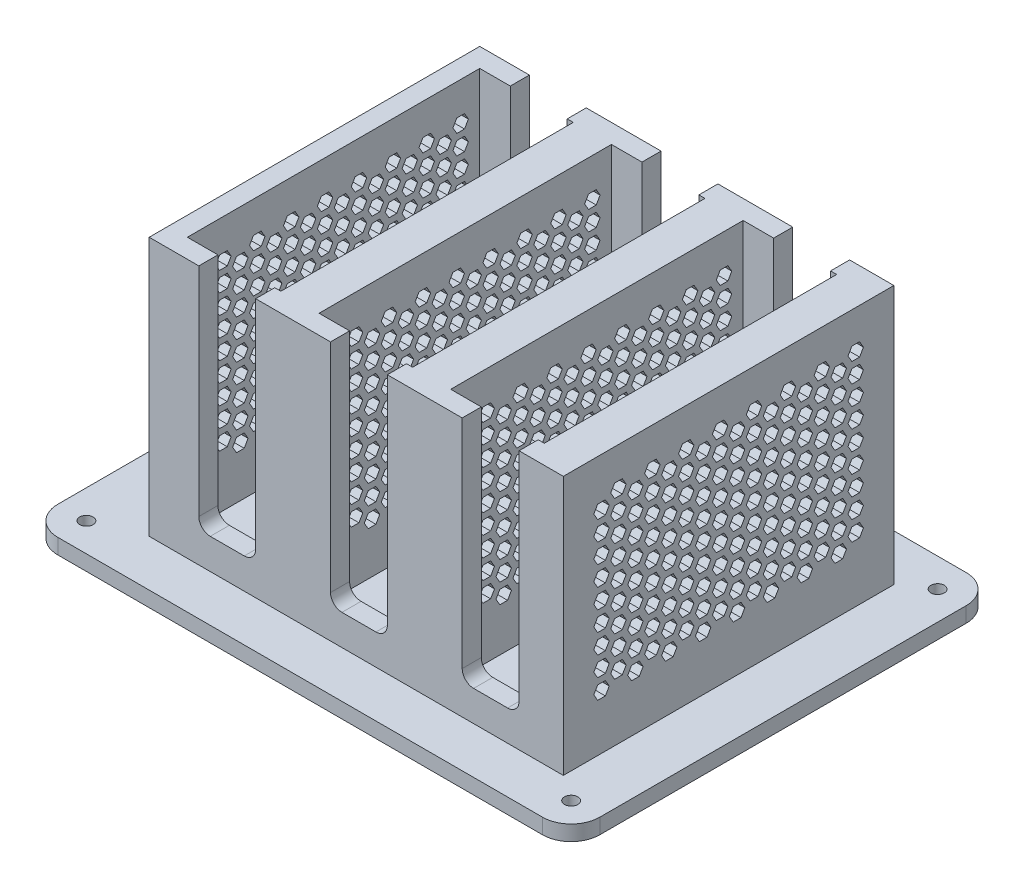
SolidWorks part; units mm, degrees
ref_plane "Front Plane" through (0, 0, 0) normal (0, 0, 1) x (1, 0, 0)
ref_plane "Top Plane" through (0, 0, 0) normal (0, 1, 0) x (1, 0, 0)
ref_plane "Right Plane" through (0, 0, 0) normal (1, 0, 0) x (0, 0, -1)
sketch "Sketch1" plane through (0, 0, 0) normal (0, 1, 0) x (1, 0, 0)
  line L1 (22.25, -38.3) -> (46.75, -38.3) construction
  line L2 (22.25, -38.3) -> (22.25, 38.3) construction
  line L3 (22.25, 38.3) -> (46.75, 38.3) construction
  line L4 (46.75, -38.3) -> (46.75, 38.3) construction
  line L5 (22.25, -38.3) -> (46.75, 38.3) construction
  line L6 (22.25, 38.3) -> (46.75, -38.3) construction
  line L10 (-12.25, 38.3) -> (12.25, 38.3) construction
  line L11 (-55, 0) -> (55, 0) construction
  line L12 (0, -55) -> (0, 55) construction
  line L13 (-71, 55.5) -> (71, -55.5) construction
  line L14 (-12.25, -38.3) -> (-12.25, 38.3) construction
  line L15 (12.25, -38.3) -> (12.25, 38.3) construction
  line L16 (-12.25, -38.3) -> (12.25, -38.3) construction
  line L17 (-46.75, 38.3) -> (-22.25, 38.3) construction
  line L18 (-46.75, -38.3) -> (-46.75, 38.3) construction
  line L19 (-22.25, -38.3) -> (-22.25, 38.3) construction
  line L20 (-46.75, -38.3) -> (-22.25, -38.3) construction
  line L21 (-12.25, 38.3) -> (12.25, -38.3) construction
  line L23 (-63.5, -55.5) -> (63.5, -55.5)
  line L24 (-71, -48) -> (-71, 48)
  line L25 (-63.5, 55.5) -> (63.5, 55.5)
  line L26 (71, -48) -> (71, 48)
  circle A0 centre (-63.5, 48) radius 1.75
  circle A1 centre (-63.5, -48) radius 1.75
  circle A2 centre (63.5, 48) radius 1.75
  circle A3 centre (63.5, -48) radius 1.75
  arc A4 (-63.5, -55.5) -> (-71, -48) centre (-63.5, -48) cw
  arc A5 (63.5, -55.5) -> (71, -48) centre (63.5, -48) ccw
  arc A6 (63.5, 55.5) -> (71, 48) centre (63.5, 48) cw
  arc A7 (-71, 48) -> (-63.5, 55.5) centre (-63.5, 48) cw
  point P0 (34.5, 0)
  point P40 (68, -48)
  point P41 (0, 0)
  point P42 (-63.6306, 48)
  dimension "D4" = 3.5
  dimension "D5" = 3
  dimension "D8" = 7.5
  dimension "D1" = 24.5
  dimension "D2" = 76.6
  dimension "D6" = 10
  dimension "D7" = 127
  dimension "D9" = 96
extrude "Boss-Extrude1" add sketch "Sketch1" along normal blind 4
sketch "Sketch5" plane through (0, 4, 0) normal (0, 1, 0) x (1, 0, 0)
  line L0 (-46.75, -38.3) -> (-46.75, 38.3)
  line L1 (-4.25, 43.3) -> (-4.25, 38.3)
  line L2 (-46.75, -38.3) -> (-38.75, -38.3)
  line L3 (-46.75, -38.3) -> (-22.25, -38.3) construction
  line L4 (-38.75, -38.3) -> (-38.75, -43.3)
  line L5 (-38.75, -43.3) -> (-51.75, -43.3)
  line L6 (-51.75, -43.3) -> (-51.75, 43.3)
  line L7 (-51.75, 43.3) -> (-38.75, 43.3)
  line L8 (-38.75, 43.3) -> (-38.75, 38.3)
  line L9 (-46.75, 38.3) -> (-22.25, 38.3) construction
  line L10 (-38.75, 38.3) -> (-46.75, 38.3)
  line L11 (-46.75, -38.3) -> (-51.75, -38.3) construction
  line L28 (-22.25, 38.3) -> (-23.85, 38.3)
  line L29 (-23.85, 38.3) -> (-23.85, 43.3)
  line L30 (-23.85, 43.3) -> (-4.25, 43.3)
  line L31 (-55, 0) -> (55, 0) construction
  line L32 (-22.25, -38.3) -> (-23.85, -38.3)
  line L33 (-23.85, -38.3) -> (-23.85, -43.3)
  line L34 (-23.85, -43.3) -> (-4.25, -43.3)
  line L35 (-12.25, 38.3) -> (12.25, 38.3) construction
  line L36 (-4.25, 38.3) -> (-12.25, 38.3)
  line L37 (-12.25, 38.3) -> (-12.25, -38.3)
  line L39 (-12.25, -38.3) -> (12.25, -38.3) construction
  line L40 (-4.25, -38.3) -> (-4.25, -43.3)
  line L41 (-22.25, -38.3) -> (-22.25, 38.3)
  line L42 (12.25, -38.3) -> (12.25, 38.3)
  line L43 (12.25, 38.3) -> (10.65, 38.3)
  line L44 (10.65, 38.3) -> (10.65, 43.3)
  line L45 (10.65, 43.3) -> (30.25, 43.3)
  line L46 (30.25, 43.3) -> (30.25, 38.3)
  line L47 (30.25, 38.3) -> (22.25, 38.3)
  line L48 (22.25, 38.3) -> (22.25, -38.3)
  line L49 (22.25, -38.3) -> (30.25, -38.3)
  line L50 (30.25, -38.3) -> (30.25, -43.3)
  line L51 (10.65, -43.3) -> (30.25, -43.3)
  line L52 (10.65, -38.3) -> (10.65, -43.3)
  line L53 (12.25, -38.3) -> (10.65, -38.3)
  line L54 (46.75, -38.3) -> (46.75, 38.3)
  line L55 (46.75, 38.3) -> (45.15, 38.3)
  line L56 (45.15, 38.3) -> (45.15, 43.3)
  line L57 (45.15, 43.3) -> (56.75, 43.3)
  line L60 (56.75, 38.3) -> (56.75, -38.3)
  line L63 (45.15, -43.3) -> (56.75, -43.3)
  line L64 (45.15, -38.3) -> (45.15, -43.3)
  line L65 (46.75, -38.3) -> (45.15, -38.3)
  line L66 (64.75, 43.3) -> (64.75, 38.3) [skipped]
  line L67 (64.75, 38.3) -> (56.75, 38.3) [skipped]
  line L68 (56.75, 38.3) -> (56.75, 43.3)
  line L69 (56.75, -38.3) -> (56.75, -43.3)
  line L70 (-12.25, -38.3) -> (-4.25, -38.3)
  line L72 (64.75, -38.3) -> (64.75, -43.3) [skipped]
  point P26 (-4.5, -46.4399)
  point P34 (-6.2339, 40.5)
  dimension "D1" = 5
  dimension "D2" = 8
  dimension "D3" = 1.6
  dimension "D4" = 3
extrude "Boss-Extrude3" add sketch "Sketch5" along normal blind 67.862
sketch "Sketch6" plane through (0, 4, 0) normal (0, 1, 0) x (1, 0, 0)
  line L1 (-51.75, -43.3) -> (56.75, -43.3)
  line L2 (-51.75, -43.3) -> (-51.75, 43.3)
  line L3 (-51.75, 43.3) -> (56.75, 43.3)
  line L4 (56.75, -43.3) -> (56.75, 43.3)
  line L5 (-46.75, -38.3) -> (46.75, -38.3)
  line L6 (-46.75, -38.3) -> (-46.75, 38.3)
  line L7 (-46.75, 38.3) -> (46.75, 38.3)
  line L8 (46.75, -38.3) -> (46.75, 38.3)
extrude "Boss-Extrude4" add sketch "Sketch6" along normal blind 8
fillet "Fillet1" radius 3 12 edges at (-23.85, 12, -40.8) (-38.75, 12, -40.8) (-4.25, 12, -40.8) (10.65, 12, -40.8) (30.25, 12, -40.8) (45.15, 12, -40.8) (45.15, 12, 40.8) (30.25, 12, 40.8) (-4.25, 12, 40.8) (10.65, 12, 40.8) (-38.75, 12, 40.8) (-23.85, 12, 40.8)
sketch "Sketch7" plane through (0, 4, 0) normal (0, 1, 0) x (1, 0, 0)
  line L0 (-46.75, 38.3) -> (-22.25, 38.3) construction
  line L1 (-46.75, -38.3) -> (-24.25, -38.3)
  line L2 (-46.75, -38.3) -> (-46.75, 38.3)
  line L3 (-46.75, 38.3) -> (-24.25, 38.3)
  line L4 (-24.25, -38.3) -> (-24.25, 38.3)
  line L5 (-22.25, -38.3) -> (-22.25, 38.3) construction
  line L6 (-12.25, -38.3) -> (-12.25, 38.3)
  line L7 (-12.25, -38.3) -> (10.25, -38.3)
  line L8 (10.25, -38.3) -> (10.25, 38.3)
  line L9 (-12.25, 38.3) -> (10.25, 38.3)
  line L10 (22.25, -38.3) -> (22.25, 38.3)
  line L11 (22.25, -38.3) -> (44.75, -38.3)
  line L12 (44.75, -38.3) -> (44.75, 38.3)
  line L13 (22.25, 38.3) -> (44.75, 38.3)
  dimension "D1" = 2
  dimension "D2" = 3
extrude "Boss-Extrude5" add sketch "Sketch7" along normal blind 1.136
sketch "Sketch8" plane through (-51.75, 0, 0) normal (-1, 0, 0) x (0, 0, 1)
  line L0 (-43.3, 71.862) -> (-43.3, 4) construction
  line L1 (-31.2793, 61.862) -> (-32.2896, 63.612)
  line L2 (-32.2896, 63.612) -> (-34.3104, 63.612)
  line L3 (-34.3104, 63.612) -> (-35.3207, 61.862)
  line L4 (-35.3207, 61.862) -> (-34.3104, 60.112)
  line L5 (-34.3104, 60.112) -> (-32.2896, 60.112)
  line L6 (-32.2896, 60.112) -> (-31.2793, 61.862)
  line L7 (-43.3, 71.862) -> (43.3, 71.862) construction
  line L8 (-22.3993, 61.862) -> (-23.4096, 63.612)
  line L9 (-23.4096, 63.612) -> (-25.4304, 63.612)
  line L10 (-25.4304, 63.612) -> (-26.4407, 61.862)
  line L11 (-26.4407, 61.862) -> (-25.4304, 60.112)
  line L12 (-25.4304, 60.112) -> (-23.4096, 60.112)
  line L13 (-23.4096, 60.112) -> (-22.3993, 61.862)
  line L14 (-13.5193, 61.862) -> (-14.5296, 63.612)
  line L15 (-14.5296, 63.612) -> (-16.5504, 63.612)
  line L16 (-16.5504, 63.612) -> (-17.5607, 61.862)
  line L17 (-17.5607, 61.862) -> (-16.5504, 60.112)
  line L18 (-16.5504, 60.112) -> (-14.5296, 60.112)
  line L19 (-14.5296, 60.112) -> (-13.5193, 61.862)
  line L20 (-4.6393, 61.862) -> (-5.6496, 63.612)
  line L21 (-5.6496, 63.612) -> (-7.6704, 63.612)
  line L22 (-7.6704, 63.612) -> (-8.6807, 61.862)
  line L23 (-8.6807, 61.862) -> (-7.6704, 60.112)
  line L24 (-7.6704, 60.112) -> (-5.6496, 60.112)
  line L25 (-5.6496, 60.112) -> (-4.6393, 61.862)
  line L26 (4.2407, 61.862) -> (3.2304, 63.612)
  line L27 (3.2304, 63.612) -> (1.2096, 63.612)
  line L28 (1.2096, 63.612) -> (0.1993, 61.862)
  line L29 (0.1993, 61.862) -> (1.2096, 60.112)
  line L30 (1.2096, 60.112) -> (3.2304, 60.112)
  line L31 (3.2304, 60.112) -> (4.2407, 61.862)
  line L32 (13.1207, 61.862) -> (12.1104, 63.612)
  line L33 (12.1104, 63.612) -> (10.0896, 63.612)
  line L34 (10.0896, 63.612) -> (9.0793, 61.862)
  line L35 (9.0793, 61.862) -> (10.0896, 60.112)
  line L36 (10.0896, 60.112) -> (12.1104, 60.112)
  line L37 (12.1104, 60.112) -> (13.1207, 61.862)
  line L38 (22.0007, 61.862) -> (20.9904, 63.612)
  line L39 (20.9904, 63.612) -> (18.9696, 63.612)
  line L40 (18.9696, 63.612) -> (17.9593, 61.862)
  line L41 (17.9593, 61.862) -> (18.9696, 60.112)
  line L42 (18.9696, 60.112) -> (20.9904, 60.112)
  line L43 (20.9904, 60.112) -> (22.0007, 61.862)
  line L44 (30.8807, 61.862) -> (29.8704, 63.612)
  line L45 (29.8704, 63.612) -> (27.8496, 63.612)
  line L46 (27.8496, 63.612) -> (26.8393, 61.862)
  line L47 (26.8393, 61.862) -> (27.8496, 60.112)
  line L48 (27.8496, 60.112) -> (29.8704, 60.112)
  line L49 (29.8704, 60.112) -> (30.8807, 61.862)
  line L80 (-27.3445, 60.1736) -> (-25.9355, 60.987) construction
  line L81 (-26.8393, 59.2986) -> (-27.8496, 61.0486)
  line L82 (-27.8496, 61.0486) -> (-29.8704, 61.0486)
  line L83 (-29.8704, 61.0486) -> (-30.8807, 59.2986)
  line L84 (-30.8807, 59.2986) -> (-29.8704, 57.5486)
  line L85 (-29.8704, 57.5486) -> (-27.8496, 57.5486)
  line L86 (-27.8496, 57.5486) -> (-26.8393, 59.2986)
  line L87 (-31.7845, 60.987) -> (-30.3755, 60.1736) construction
  line L88 (-17.9593, 59.2986) -> (-18.9696, 61.0486)
  line L89 (-18.9696, 61.0486) -> (-20.9904, 61.0486)
  line L90 (-20.9904, 61.0486) -> (-22.0007, 59.2986)
  line L91 (-22.0007, 59.2986) -> (-20.9904, 57.5486)
  line L92 (-20.9904, 57.5486) -> (-18.9696, 57.5486)
  line L93 (-18.9696, 57.5486) -> (-17.9593, 59.2986)
  line L94 (-9.0793, 59.2986) -> (-10.0896, 61.0486)
  line L95 (-10.0896, 61.0486) -> (-12.1104, 61.0486)
  line L96 (-12.1104, 61.0486) -> (-13.1207, 59.2986)
  line L97 (-13.1207, 59.2986) -> (-12.1104, 57.5486)
  line L98 (-12.1104, 57.5486) -> (-10.0896, 57.5486)
  line L99 (-10.0896, 57.5486) -> (-9.0793, 59.2986)
  line L100 (-0.1993, 59.2986) -> (-1.2096, 61.0486)
  line L101 (-1.2096, 61.0486) -> (-3.2304, 61.0486)
  line L102 (-3.2304, 61.0486) -> (-4.2407, 59.2986)
  line L103 (-4.2407, 59.2986) -> (-3.2304, 57.5486)
  line L104 (-3.2304, 57.5486) -> (-1.2096, 57.5486)
  line L105 (-1.2096, 57.5486) -> (-0.1993, 59.2986)
  line L106 (8.6807, 59.2986) -> (7.6704, 61.0486)
  line L107 (7.6704, 61.0486) -> (5.6496, 61.0486)
  line L108 (5.6496, 61.0486) -> (4.6393, 59.2986)
  line L109 (4.6393, 59.2986) -> (5.6496, 57.5486)
  line L110 (5.6496, 57.5486) -> (7.6704, 57.5486)
  line L111 (7.6704, 57.5486) -> (8.6807, 59.2986)
  line L112 (17.5607, 59.2986) -> (16.5504, 61.0486)
  line L113 (16.5504, 61.0486) -> (14.5296, 61.0486)
  line L114 (14.5296, 61.0486) -> (13.5193, 59.2986)
  line L115 (13.5193, 59.2986) -> (14.5296, 57.5486)
  line L116 (14.5296, 57.5486) -> (16.5504, 57.5486)
  line L117 (16.5504, 57.5486) -> (17.5607, 59.2986)
  line L118 (26.4407, 59.2986) -> (25.4304, 61.0486)
  line L119 (25.4304, 61.0486) -> (23.4096, 61.0486)
  line L120 (23.4096, 61.0486) -> (22.3993, 59.2986)
  line L121 (22.3993, 59.2986) -> (23.4096, 57.5486)
  line L122 (23.4096, 57.5486) -> (25.4304, 57.5486)
  line L123 (25.4304, 57.5486) -> (26.4407, 59.2986)
  line L124 (35.3207, 59.2986) -> (34.3104, 61.0486)
  line L125 (34.3104, 61.0486) -> (32.2896, 61.0486)
  line L126 (32.2896, 61.0486) -> (31.2793, 59.2986)
  line L127 (31.2793, 59.2986) -> (32.2896, 57.5486)
  line L128 (32.2896, 57.5486) -> (34.3104, 57.5486)
  line L129 (34.3104, 57.5486) -> (35.3207, 59.2986)
  line L154 (-31.2793, 56.7351) -> (-32.2896, 58.4851)
  line L155 (-32.2896, 58.4851) -> (-34.3104, 58.4851)
  line L156 (-34.3104, 58.4851) -> (-35.3207, 56.7351)
  line L157 (-21.4955, 60.1736) -> (-22.9045, 60.987) construction
  line L158 (-35.3207, 56.7351) -> (-34.3104, 54.9851)
  line L159 (-34.3104, 54.9851) -> (-32.2896, 54.9851)
  line L160 (-32.2896, 54.9851) -> (-31.2793, 56.7351)
  line L161 (33.3, 61.0486) -> (33.3, 59.2986) construction
  line L162 (33.3, 59.2986) -> (35.3207, 59.2986) construction
  line L163 (43.3, 71.862) -> (43.3, 4) construction
  line L164 (-22.3993, 56.7351) -> (-23.4096, 58.4851)
  line L165 (-23.4096, 58.4851) -> (-25.4304, 58.4851)
  line L166 (-25.4304, 58.4851) -> (-26.4407, 56.7351)
  line L167 (-26.4407, 56.7351) -> (-25.4304, 54.9851)
  line L168 (-25.4304, 54.9851) -> (-23.4096, 54.9851)
  line L169 (-23.4096, 54.9851) -> (-22.3993, 56.7351)
  line L170 (-13.5193, 56.7351) -> (-14.5296, 58.4851)
  line L171 (-14.5296, 58.4851) -> (-16.5504, 58.4851)
  line L172 (-16.5504, 58.4851) -> (-17.5607, 56.7351)
  line L173 (-17.5607, 56.7351) -> (-16.5504, 54.9851)
  line L174 (-16.5504, 54.9851) -> (-14.5296, 54.9851)
  line L175 (-14.5296, 54.9851) -> (-13.5193, 56.7351)
  line L176 (-4.6393, 56.7351) -> (-5.6496, 58.4851)
  line L177 (-5.6496, 58.4851) -> (-7.6704, 58.4851)
  line L178 (-7.6704, 58.4851) -> (-8.6807, 56.7351)
  line L179 (-8.6807, 56.7351) -> (-7.6704, 54.9851)
  line L180 (-7.6704, 54.9851) -> (-5.6496, 54.9851)
  line L181 (-5.6496, 54.9851) -> (-4.6393, 56.7351)
  line L182 (4.2407, 56.7351) -> (3.2304, 58.4851)
  line L183 (3.2304, 58.4851) -> (1.2096, 58.4851)
  line L184 (1.2096, 58.4851) -> (0.1993, 56.7351)
  line L185 (0.1993, 56.7351) -> (1.2096, 54.9851)
  line L186 (1.2096, 54.9851) -> (3.2304, 54.9851)
  line L187 (3.2304, 54.9851) -> (4.2407, 56.7351)
  line L188 (13.1207, 56.7351) -> (12.1104, 58.4851)
  line L189 (12.1104, 58.4851) -> (10.0896, 58.4851)
  line L190 (10.0896, 58.4851) -> (9.0793, 56.7351)
  line L191 (9.0793, 56.7351) -> (10.0896, 54.9851)
  line L192 (10.0896, 54.9851) -> (12.1104, 54.9851)
  line L193 (12.1104, 54.9851) -> (13.1207, 56.7351)
  line L194 (22.0007, 56.7351) -> (20.9904, 58.4851)
  line L195 (20.9904, 58.4851) -> (18.9696, 58.4851)
  line L196 (18.9696, 58.4851) -> (17.9593, 56.7351)
  line L197 (17.9593, 56.7351) -> (18.9696, 54.9851)
  line L198 (18.9696, 54.9851) -> (20.9904, 54.9851)
  line L199 (20.9904, 54.9851) -> (22.0007, 56.7351)
  line L200 (30.8807, 56.7351) -> (29.8704, 58.4851)
  line L201 (29.8704, 58.4851) -> (27.8496, 58.4851)
  line L202 (27.8496, 58.4851) -> (26.8393, 56.7351)
  line L203 (26.8393, 56.7351) -> (27.8496, 54.9851)
  line L204 (27.8496, 54.9851) -> (29.8704, 54.9851)
  line L205 (29.8704, 54.9851) -> (30.8807, 56.7351)
  line L206 (-26.8393, 54.1717) -> (-27.8496, 55.9217)
  line L207 (-27.8496, 55.9217) -> (-29.8704, 55.9217)
  line L208 (-29.8704, 55.9217) -> (-30.8807, 54.1717)
  line L209 (-30.8807, 54.1717) -> (-29.8704, 52.4217)
  line L210 (-29.8704, 52.4217) -> (-27.8496, 52.4217)
  line L211 (-27.8496, 52.4217) -> (-26.8393, 54.1717)
  line L212 (-17.9593, 54.1717) -> (-18.9696, 55.9217)
  line L213 (-18.9696, 55.9217) -> (-20.9904, 55.9217)
  line L214 (-20.9904, 55.9217) -> (-22.0007, 54.1717)
  line L215 (-22.0007, 54.1717) -> (-20.9904, 52.4217)
  line L216 (-20.9904, 52.4217) -> (-18.9696, 52.4217)
  line L217 (-18.9696, 52.4217) -> (-17.9593, 54.1717)
  line L218 (-9.0793, 54.1717) -> (-10.0896, 55.9217)
  line L219 (-10.0896, 55.9217) -> (-12.1104, 55.9217)
  line L220 (-12.1104, 55.9217) -> (-13.1207, 54.1717)
  line L221 (-13.1207, 54.1717) -> (-12.1104, 52.4217)
  line L222 (-12.1104, 52.4217) -> (-10.0896, 52.4217)
  line L223 (-10.0896, 52.4217) -> (-9.0793, 54.1717)
  line L224 (-0.1993, 54.1717) -> (-1.2096, 55.9217)
  line L225 (-1.2096, 55.9217) -> (-3.2304, 55.9217)
  line L226 (-3.2304, 55.9217) -> (-4.2407, 54.1717)
  line L227 (-4.2407, 54.1717) -> (-3.2304, 52.4217)
  line L228 (-3.2304, 52.4217) -> (-1.2096, 52.4217)
  line L229 (-1.2096, 52.4217) -> (-0.1993, 54.1717)
  line L230 (8.6807, 54.1717) -> (7.6704, 55.9217)
  line L231 (7.6704, 55.9217) -> (5.6496, 55.9217)
  line L232 (5.6496, 55.9217) -> (4.6393, 54.1717)
  line L233 (4.6393, 54.1717) -> (5.6496, 52.4217)
  line L234 (5.6496, 52.4217) -> (7.6704, 52.4217)
  line L235 (7.6704, 52.4217) -> (8.6807, 54.1717)
  line L236 (17.5607, 54.1717) -> (16.5504, 55.9217)
  line L237 (16.5504, 55.9217) -> (14.5296, 55.9217)
  line L238 (14.5296, 55.9217) -> (13.5193, 54.1717)
  line L239 (13.5193, 54.1717) -> (14.5296, 52.4217)
  line L240 (14.5296, 52.4217) -> (16.5504, 52.4217)
  line L241 (16.5504, 52.4217) -> (17.5607, 54.1717)
  line L242 (26.4407, 54.1717) -> (25.4304, 55.9217)
  line L243 (25.4304, 55.9217) -> (23.4096, 55.9217)
  line L244 (23.4096, 55.9217) -> (22.3993, 54.1717)
  line L245 (22.3993, 54.1717) -> (23.4096, 52.4217)
  line L246 (23.4096, 52.4217) -> (25.4304, 52.4217)
  line L247 (25.4304, 52.4217) -> (26.4407, 54.1717)
  line L248 (35.3207, 54.1717) -> (34.3104, 55.9217)
  line L249 (34.3104, 55.9217) -> (32.2896, 55.9217)
  line L250 (32.2896, 55.9217) -> (31.2793, 54.1717)
  line L251 (31.2793, 54.1717) -> (32.2896, 52.4217)
  line L252 (32.2896, 52.4217) -> (34.3104, 52.4217)
  line L253 (34.3104, 52.4217) -> (35.3207, 54.1717)
  line L254 (-27.3445, 55.0467) -> (-25.9355, 55.8601) construction
  line L255 (-31.7845, 55.8601) -> (-30.3755, 55.0467) construction
  line L256 (-21.4955, 55.0467) -> (-22.9045, 55.8601) construction
  line L257 (33.3, 55.9217) -> (33.3, 54.1717) construction
  line L258 (33.3, 54.1717) -> (35.3207, 54.1717) construction
  line L259 (-31.2793, 51.6083) -> (-32.2896, 53.3583)
  line L260 (-32.2896, 53.3583) -> (-34.3104, 53.3583)
  line L261 (-34.3104, 53.3583) -> (-35.3207, 51.6083)
  line L262 (-35.3207, 51.6083) -> (-34.3104, 49.8583)
  line L263 (-34.3104, 49.8583) -> (-32.2896, 49.8583)
  line L264 (-32.2896, 49.8583) -> (-31.2793, 51.6083)
  line L265 (-22.3993, 51.6083) -> (-23.4096, 53.3583)
  line L266 (-23.4096, 53.3583) -> (-25.4304, 53.3583)
  line L267 (-25.4304, 53.3583) -> (-26.4407, 51.6083)
  line L268 (-26.4407, 51.6083) -> (-25.4304, 49.8583)
  line L269 (-25.4304, 49.8583) -> (-23.4096, 49.8583)
  line L270 (-23.4096, 49.8583) -> (-22.3993, 51.6083)
  line L271 (-13.5193, 51.6083) -> (-14.5296, 53.3583)
  line L272 (-14.5296, 53.3583) -> (-16.5504, 53.3583)
  line L273 (-16.5504, 53.3583) -> (-17.5607, 51.6083)
  line L274 (-17.5607, 51.6083) -> (-16.5504, 49.8583)
  line L275 (-16.5504, 49.8583) -> (-14.5296, 49.8583)
  line L276 (-14.5296, 49.8583) -> (-13.5193, 51.6083)
  line L277 (-4.6393, 51.6083) -> (-5.6496, 53.3583)
  line L278 (-5.6496, 53.3583) -> (-7.6704, 53.3583)
  line L279 (-7.6704, 53.3583) -> (-8.6807, 51.6083)
  line L280 (-8.6807, 51.6083) -> (-7.6704, 49.8583)
  line L281 (-7.6704, 49.8583) -> (-5.6496, 49.8583)
  line L282 (-5.6496, 49.8583) -> (-4.6393, 51.6083)
  line L283 (4.2407, 51.6083) -> (3.2304, 53.3583)
  line L284 (3.2304, 53.3583) -> (1.2096, 53.3583)
  line L285 (1.2096, 53.3583) -> (0.1993, 51.6083)
  line L286 (0.1993, 51.6083) -> (1.2096, 49.8583)
  line L287 (1.2096, 49.8583) -> (3.2304, 49.8583)
  line L288 (3.2304, 49.8583) -> (4.2407, 51.6083)
  line L289 (13.1207, 51.6083) -> (12.1104, 53.3583)
  line L290 (12.1104, 53.3583) -> (10.0896, 53.3583)
  line L291 (10.0896, 53.3583) -> (9.0793, 51.6083)
  line L292 (9.0793, 51.6083) -> (10.0896, 49.8583)
  line L293 (10.0896, 49.8583) -> (12.1104, 49.8583)
  line L294 (12.1104, 49.8583) -> (13.1207, 51.6083)
  line L295 (22.0007, 51.6083) -> (20.9904, 53.3583)
  line L296 (20.9904, 53.3583) -> (18.9696, 53.3583)
  line L297 (18.9696, 53.3583) -> (17.9593, 51.6083)
  line L298 (17.9593, 51.6083) -> (18.9696, 49.8583)
  line L299 (18.9696, 49.8583) -> (20.9904, 49.8583)
  line L300 (20.9904, 49.8583) -> (22.0007, 51.6083)
  line L301 (30.8807, 51.6083) -> (29.8704, 53.3583)
  line L302 (29.8704, 53.3583) -> (27.8496, 53.3583)
  line L303 (27.8496, 53.3583) -> (26.8393, 51.6083)
  line L304 (26.8393, 51.6083) -> (27.8496, 49.8583)
  line L305 (27.8496, 49.8583) -> (29.8704, 49.8583)
  line L306 (29.8704, 49.8583) -> (30.8807, 51.6083)
  line L307 (-26.8393, 49.0448) -> (-27.8496, 50.7948)
  line L308 (-27.8496, 50.7948) -> (-29.8704, 50.7948)
  line L309 (-29.8704, 50.7948) -> (-30.8807, 49.0448)
  line L310 (-30.8807, 49.0448) -> (-29.8704, 47.2948)
  line L311 (-29.8704, 47.2948) -> (-27.8496, 47.2948)
  line L312 (-27.8496, 47.2948) -> (-26.8393, 49.0448)
  line L313 (-17.9593, 49.0448) -> (-18.9696, 50.7948)
  line L314 (-18.9696, 50.7948) -> (-20.9904, 50.7948)
  line L315 (-20.9904, 50.7948) -> (-22.0007, 49.0448)
  line L316 (-22.0007, 49.0448) -> (-20.9904, 47.2948)
  line L317 (-20.9904, 47.2948) -> (-18.9696, 47.2948)
  line L318 (-18.9696, 47.2948) -> (-17.9593, 49.0448)
  line L319 (-9.0793, 49.0448) -> (-10.0896, 50.7948)
  line L320 (-10.0896, 50.7948) -> (-12.1104, 50.7948)
  line L321 (-12.1104, 50.7948) -> (-13.1207, 49.0448)
  line L322 (-13.1207, 49.0448) -> (-12.1104, 47.2948)
  line L323 (-12.1104, 47.2948) -> (-10.0896, 47.2948)
  line L324 (-10.0896, 47.2948) -> (-9.0793, 49.0448)
  line L325 (-0.1993, 49.0448) -> (-1.2096, 50.7948)
  line L326 (-1.2096, 50.7948) -> (-3.2304, 50.7948)
  line L327 (-3.2304, 50.7948) -> (-4.2407, 49.0448)
  line L328 (-4.2407, 49.0448) -> (-3.2304, 47.2948)
  line L329 (-3.2304, 47.2948) -> (-1.2096, 47.2948)
  line L330 (-1.2096, 47.2948) -> (-0.1993, 49.0448)
  line L331 (8.6807, 49.0448) -> (7.6704, 50.7948)
  line L332 (7.6704, 50.7948) -> (5.6496, 50.7948)
  line L333 (5.6496, 50.7948) -> (4.6393, 49.0448)
  line L334 (4.6393, 49.0448) -> (5.6496, 47.2948)
  line L335 (5.6496, 47.2948) -> (7.6704, 47.2948)
  line L336 (7.6704, 47.2948) -> (8.6807, 49.0448)
  line L337 (17.5607, 49.0448) -> (16.5504, 50.7948)
  line L338 (16.5504, 50.7948) -> (14.5296, 50.7948)
  line L339 (14.5296, 50.7948) -> (13.5193, 49.0448)
  line L340 (13.5193, 49.0448) -> (14.5296, 47.2948)
  line L341 (14.5296, 47.2948) -> (16.5504, 47.2948)
  line L342 (16.5504, 47.2948) -> (17.5607, 49.0448)
  line L343 (26.4407, 49.0448) -> (25.4304, 50.7948)
  line L344 (25.4304, 50.7948) -> (23.4096, 50.7948)
  line L345 (23.4096, 50.7948) -> (22.3993, 49.0448)
  line L346 (22.3993, 49.0448) -> (23.4096, 47.2948)
  line L347 (23.4096, 47.2948) -> (25.4304, 47.2948)
  line L348 (25.4304, 47.2948) -> (26.4407, 49.0448)
  line L349 (35.3207, 49.0448) -> (34.3104, 50.7948)
  line L350 (34.3104, 50.7948) -> (32.2896, 50.7948)
  line L351 (32.2896, 50.7948) -> (31.2793, 49.0448)
  line L352 (31.2793, 49.0448) -> (32.2896, 47.2948)
  line L353 (32.2896, 47.2948) -> (34.3104, 47.2948)
  line L354 (34.3104, 47.2948) -> (35.3207, 49.0448)
  line L355 (-27.3445, 49.9198) -> (-25.9355, 50.7333) construction
  line L356 (-31.7845, 50.7333) -> (-30.3755, 49.9198) construction
  line L357 (-21.4955, 49.9198) -> (-22.9045, 50.7333) construction
  line L358 (33.3, 50.7948) -> (33.3, 49.0448) construction
  line L359 (33.3, 49.0448) -> (35.3207, 49.0448) construction
  line L360 (-31.2793, 46.4814) -> (-32.2896, 48.2314)
  line L361 (-32.2896, 48.2314) -> (-34.3104, 48.2314)
  line L362 (-34.3104, 48.2314) -> (-35.3207, 46.4814)
  line L363 (-35.3207, 46.4814) -> (-34.3104, 44.7314)
  line L364 (-34.3104, 44.7314) -> (-32.2896, 44.7314)
  line L365 (-32.2896, 44.7314) -> (-31.2793, 46.4814)
  line L366 (-22.3993, 46.4814) -> (-23.4096, 48.2314)
  line L367 (-23.4096, 48.2314) -> (-25.4304, 48.2314)
  line L368 (-25.4304, 48.2314) -> (-26.4407, 46.4814)
  line L369 (-26.4407, 46.4814) -> (-25.4304, 44.7314)
  line L370 (-25.4304, 44.7314) -> (-23.4096, 44.7314)
  line L371 (-23.4096, 44.7314) -> (-22.3993, 46.4814)
  line L372 (-13.5193, 46.4814) -> (-14.5296, 48.2314)
  line L373 (-14.5296, 48.2314) -> (-16.5504, 48.2314)
  line L374 (-16.5504, 48.2314) -> (-17.5607, 46.4814)
  line L375 (-17.5607, 46.4814) -> (-16.5504, 44.7314)
  line L376 (-16.5504, 44.7314) -> (-14.5296, 44.7314)
  line L377 (-14.5296, 44.7314) -> (-13.5193, 46.4814)
  line L378 (-4.6393, 46.4814) -> (-5.6496, 48.2314)
  line L379 (-5.6496, 48.2314) -> (-7.6704, 48.2314)
  line L380 (-7.6704, 48.2314) -> (-8.6807, 46.4814)
  line L381 (-8.6807, 46.4814) -> (-7.6704, 44.7314)
  line L382 (-7.6704, 44.7314) -> (-5.6496, 44.7314)
  line L383 (-5.6496, 44.7314) -> (-4.6393, 46.4814)
  line L384 (4.2407, 46.4814) -> (3.2304, 48.2314)
  line L385 (3.2304, 48.2314) -> (1.2096, 48.2314)
  line L386 (1.2096, 48.2314) -> (0.1993, 46.4814)
  line L387 (0.1993, 46.4814) -> (1.2096, 44.7314)
  line L388 (1.2096, 44.7314) -> (3.2304, 44.7314)
  line L389 (3.2304, 44.7314) -> (4.2407, 46.4814)
  line L390 (13.1207, 46.4814) -> (12.1104, 48.2314)
  line L391 (12.1104, 48.2314) -> (10.0896, 48.2314)
  line L392 (10.0896, 48.2314) -> (9.0793, 46.4814)
  line L393 (9.0793, 46.4814) -> (10.0896, 44.7314)
  line L394 (10.0896, 44.7314) -> (12.1104, 44.7314)
  line L395 (12.1104, 44.7314) -> (13.1207, 46.4814)
  line L396 (22.0007, 46.4814) -> (20.9904, 48.2314)
  line L397 (20.9904, 48.2314) -> (18.9696, 48.2314)
  line L398 (18.9696, 48.2314) -> (17.9593, 46.4814)
  line L399 (17.9593, 46.4814) -> (18.9696, 44.7314)
  line L400 (18.9696, 44.7314) -> (20.9904, 44.7314)
  line L401 (20.9904, 44.7314) -> (22.0007, 46.4814)
  line L402 (30.8807, 46.4814) -> (29.8704, 48.2314)
  line L403 (29.8704, 48.2314) -> (27.8496, 48.2314)
  line L404 (27.8496, 48.2314) -> (26.8393, 46.4814)
  line L405 (26.8393, 46.4814) -> (27.8496, 44.7314)
  line L406 (27.8496, 44.7314) -> (29.8704, 44.7314)
  line L407 (29.8704, 44.7314) -> (30.8807, 46.4814)
  line L408 (-26.8393, 43.918) -> (-27.8496, 45.668)
  line L409 (-27.8496, 45.668) -> (-29.8704, 45.668)
  line L410 (-29.8704, 45.668) -> (-30.8807, 43.918)
  line L411 (-30.8807, 43.918) -> (-29.8704, 42.168)
  line L412 (-29.8704, 42.168) -> (-27.8496, 42.168)
  line L413 (-27.8496, 42.168) -> (-26.8393, 43.918)
  line L414 (-17.9593, 43.918) -> (-18.9696, 45.668)
  line L415 (-18.9696, 45.668) -> (-20.9904, 45.668)
  line L416 (-20.9904, 45.668) -> (-22.0007, 43.918)
  line L417 (-22.0007, 43.918) -> (-20.9904, 42.168)
  line L418 (-20.9904, 42.168) -> (-18.9696, 42.168)
  line L419 (-18.9696, 42.168) -> (-17.9593, 43.918)
  line L420 (-9.0793, 43.918) -> (-10.0896, 45.668)
  line L421 (-10.0896, 45.668) -> (-12.1104, 45.668)
  line L422 (-12.1104, 45.668) -> (-13.1207, 43.918)
  line L423 (-13.1207, 43.918) -> (-12.1104, 42.168)
  line L424 (-12.1104, 42.168) -> (-10.0896, 42.168)
  line L425 (-10.0896, 42.168) -> (-9.0793, 43.918)
  line L426 (-0.1993, 43.918) -> (-1.2096, 45.668)
  line L427 (-1.2096, 45.668) -> (-3.2304, 45.668)
  line L428 (-3.2304, 45.668) -> (-4.2407, 43.918)
  line L429 (-4.2407, 43.918) -> (-3.2304, 42.168)
  line L430 (-3.2304, 42.168) -> (-1.2096, 42.168)
  line L431 (-1.2096, 42.168) -> (-0.1993, 43.918)
  line L432 (8.6807, 43.918) -> (7.6704, 45.668)
  line L433 (7.6704, 45.668) -> (5.6496, 45.668)
  line L434 (5.6496, 45.668) -> (4.6393, 43.918)
  line L435 (4.6393, 43.918) -> (5.6496, 42.168)
  line L436 (5.6496, 42.168) -> (7.6704, 42.168)
  line L437 (7.6704, 42.168) -> (8.6807, 43.918)
  line L438 (17.5607, 43.918) -> (16.5504, 45.668)
  line L439 (16.5504, 45.668) -> (14.5296, 45.668)
  line L440 (14.5296, 45.668) -> (13.5193, 43.918)
  line L441 (13.5193, 43.918) -> (14.5296, 42.168)
  line L442 (14.5296, 42.168) -> (16.5504, 42.168)
  line L443 (16.5504, 42.168) -> (17.5607, 43.918)
  line L444 (26.4407, 43.918) -> (25.4304, 45.668)
  line L445 (25.4304, 45.668) -> (23.4096, 45.668)
  line L446 (23.4096, 45.668) -> (22.3993, 43.918)
  line L447 (22.3993, 43.918) -> (23.4096, 42.168)
  line L448 (23.4096, 42.168) -> (25.4304, 42.168)
  line L449 (25.4304, 42.168) -> (26.4407, 43.918)
  line L450 (35.3207, 43.918) -> (34.3104, 45.668)
  line L451 (34.3104, 45.668) -> (32.2896, 45.668)
  line L452 (32.2896, 45.668) -> (31.2793, 43.918)
  line L453 (31.2793, 43.918) -> (32.2896, 42.168)
  line L454 (32.2896, 42.168) -> (34.3104, 42.168)
  line L455 (34.3104, 42.168) -> (35.3207, 43.918)
  line L456 (-27.3445, 44.793) -> (-25.9355, 45.6064) construction
  line L457 (-31.7845, 45.6064) -> (-30.3755, 44.793) construction
  line L458 (-21.4955, 44.793) -> (-22.9045, 45.6064) construction
  line L459 (33.3, 45.668) -> (33.3, 43.918) construction
  line L460 (33.3, 43.918) -> (35.3207, 43.918) construction
  line L461 (-31.7845, 57.6101) -> (-30.3755, 58.4236) construction
  line L462 (-31.2793, 41.3545) -> (-32.2896, 43.1045)
  line L463 (-32.2896, 43.1045) -> (-34.3104, 43.1045)
  line L464 (-34.3104, 43.1045) -> (-35.3207, 41.3545)
  line L465 (-35.3207, 41.3545) -> (-34.3104, 39.6045)
  line L466 (-34.3104, 39.6045) -> (-32.2896, 39.6045)
  line L467 (-32.2896, 39.6045) -> (-31.2793, 41.3545)
  line L468 (-22.3993, 41.3545) -> (-23.4096, 43.1045)
  line L469 (-23.4096, 43.1045) -> (-25.4304, 43.1045)
  line L470 (-25.4304, 43.1045) -> (-26.4407, 41.3545)
  line L471 (-26.4407, 41.3545) -> (-25.4304, 39.6045)
  line L472 (-25.4304, 39.6045) -> (-23.4096, 39.6045)
  line L473 (-23.4096, 39.6045) -> (-22.3993, 41.3545)
  line L474 (-13.5193, 41.3545) -> (-14.5296, 43.1045)
  line L475 (-14.5296, 43.1045) -> (-16.5504, 43.1045)
  line L476 (-16.5504, 43.1045) -> (-17.5607, 41.3545)
  line L477 (-17.5607, 41.3545) -> (-16.5504, 39.6045)
  line L478 (-16.5504, 39.6045) -> (-14.5296, 39.6045)
  line L479 (-14.5296, 39.6045) -> (-13.5193, 41.3545)
  line L480 (-4.6393, 41.3545) -> (-5.6496, 43.1045)
  line L481 (-5.6496, 43.1045) -> (-7.6704, 43.1045)
  line L482 (-7.6704, 43.1045) -> (-8.6807, 41.3545)
  line L483 (-8.6807, 41.3545) -> (-7.6704, 39.6045)
  line L484 (-7.6704, 39.6045) -> (-5.6496, 39.6045)
  line L485 (-5.6496, 39.6045) -> (-4.6393, 41.3545)
  line L486 (4.2407, 41.3545) -> (3.2304, 43.1045)
  line L487 (3.2304, 43.1045) -> (1.2096, 43.1045)
  line L488 (1.2096, 43.1045) -> (0.1993, 41.3545)
  line L489 (0.1993, 41.3545) -> (1.2096, 39.6045)
  line L490 (1.2096, 39.6045) -> (3.2304, 39.6045)
  line L491 (3.2304, 39.6045) -> (4.2407, 41.3545)
  line L492 (13.1207, 41.3545) -> (12.1104, 43.1045)
  line L493 (12.1104, 43.1045) -> (10.0896, 43.1045)
  line L494 (10.0896, 43.1045) -> (9.0793, 41.3545)
  line L495 (9.0793, 41.3545) -> (10.0896, 39.6045)
  line L496 (10.0896, 39.6045) -> (12.1104, 39.6045)
  line L497 (12.1104, 39.6045) -> (13.1207, 41.3545)
  line L498 (22.0007, 41.3545) -> (20.9904, 43.1045)
  line L499 (20.9904, 43.1045) -> (18.9696, 43.1045)
  line L500 (18.9696, 43.1045) -> (17.9593, 41.3545)
  line L501 (17.9593, 41.3545) -> (18.9696, 39.6045)
  line L502 (18.9696, 39.6045) -> (20.9904, 39.6045)
  line L503 (20.9904, 39.6045) -> (22.0007, 41.3545)
  line L504 (30.8807, 41.3545) -> (29.8704, 43.1045)
  line L505 (29.8704, 43.1045) -> (27.8496, 43.1045)
  line L506 (27.8496, 43.1045) -> (26.8393, 41.3545)
  line L507 (26.8393, 41.3545) -> (27.8496, 39.6045)
  line L508 (27.8496, 39.6045) -> (29.8704, 39.6045)
  line L509 (29.8704, 39.6045) -> (30.8807, 41.3545)
  line L510 (-26.8393, 38.7911) -> (-27.8496, 40.5411)
  line L511 (-27.8496, 40.5411) -> (-29.8704, 40.5411)
  line L512 (-29.8704, 40.5411) -> (-30.8807, 38.7911)
  line L513 (-30.8807, 38.7911) -> (-29.8704, 37.0411)
  line L514 (-29.8704, 37.0411) -> (-27.8496, 37.0411)
  line L515 (-27.8496, 37.0411) -> (-26.8393, 38.7911)
  line L516 (-17.9593, 38.7911) -> (-18.9696, 40.5411)
  line L517 (-18.9696, 40.5411) -> (-20.9904, 40.5411)
  line L518 (-20.9904, 40.5411) -> (-22.0007, 38.7911)
  line L519 (-22.0007, 38.7911) -> (-20.9904, 37.0411)
  line L520 (-20.9904, 37.0411) -> (-18.9696, 37.0411)
  line L521 (-18.9696, 37.0411) -> (-17.9593, 38.7911)
  line L522 (-9.0793, 38.7911) -> (-10.0896, 40.5411)
  line L523 (-10.0896, 40.5411) -> (-12.1104, 40.5411)
  line L524 (-12.1104, 40.5411) -> (-13.1207, 38.7911)
  line L525 (-13.1207, 38.7911) -> (-12.1104, 37.0411)
  line L526 (-12.1104, 37.0411) -> (-10.0896, 37.0411)
  line L527 (-10.0896, 37.0411) -> (-9.0793, 38.7911)
  line L528 (-0.1993, 38.7911) -> (-1.2096, 40.5411)
  line L529 (-1.2096, 40.5411) -> (-3.2304, 40.5411)
  line L530 (-3.2304, 40.5411) -> (-4.2407, 38.7911)
  line L531 (-4.2407, 38.7911) -> (-3.2304, 37.0411)
  line L532 (-3.2304, 37.0411) -> (-1.2096, 37.0411)
  line L533 (-1.2096, 37.0411) -> (-0.1993, 38.7911)
  line L534 (8.6807, 38.7911) -> (7.6704, 40.5411)
  line L535 (7.6704, 40.5411) -> (5.6496, 40.5411)
  line L536 (5.6496, 40.5411) -> (4.6393, 38.7911)
  line L537 (4.6393, 38.7911) -> (5.6496, 37.0411)
  line L538 (5.6496, 37.0411) -> (7.6704, 37.0411)
  line L539 (7.6704, 37.0411) -> (8.6807, 38.7911)
  line L540 (17.5607, 38.7911) -> (16.5504, 40.5411)
  line L541 (16.5504, 40.5411) -> (14.5296, 40.5411)
  line L542 (14.5296, 40.5411) -> (13.5193, 38.7911)
  line L543 (13.5193, 38.7911) -> (14.5296, 37.0411)
  line L544 (14.5296, 37.0411) -> (16.5504, 37.0411)
  line L545 (16.5504, 37.0411) -> (17.5607, 38.7911)
  line L546 (26.4407, 38.7911) -> (25.4304, 40.5411)
  line L547 (25.4304, 40.5411) -> (23.4096, 40.5411)
  line L548 (23.4096, 40.5411) -> (22.3993, 38.7911)
  line L549 (22.3993, 38.7911) -> (23.4096, 37.0411)
  line L550 (23.4096, 37.0411) -> (25.4304, 37.0411)
  line L551 (25.4304, 37.0411) -> (26.4407, 38.7911)
  line L552 (35.3207, 38.7911) -> (34.3104, 40.5411)
  line L553 (34.3104, 40.5411) -> (32.2896, 40.5411)
  line L554 (32.2896, 40.5411) -> (31.2793, 38.7911)
  line L555 (31.2793, 38.7911) -> (32.2896, 37.0411)
  line L556 (32.2896, 37.0411) -> (34.3104, 37.0411)
  line L557 (34.3104, 37.0411) -> (35.3207, 38.7911)
  line L558 (-27.3445, 39.6661) -> (-25.9355, 40.4795) construction
  line L559 (-31.7845, 40.4795) -> (-30.3755, 39.6661) construction
  line L560 (-21.4955, 39.6661) -> (-22.9045, 40.4795) construction
  line L561 (33.3, 40.5411) -> (33.3, 38.7911) construction
  line L562 (33.3, 38.7911) -> (35.3207, 38.7911) construction
  line L563 (-31.2793, 36.2276) -> (-32.2896, 37.9776)
  line L564 (-32.2896, 37.9776) -> (-34.3104, 37.9776)
  line L565 (-34.3104, 37.9776) -> (-35.3207, 36.2276)
  line L566 (-35.3207, 36.2276) -> (-34.3104, 34.4776)
  line L567 (-34.3104, 34.4776) -> (-32.2896, 34.4776)
  line L568 (-32.2896, 34.4776) -> (-31.2793, 36.2276)
  line L569 (-22.3993, 36.2276) -> (-23.4096, 37.9776)
  line L570 (-23.4096, 37.9776) -> (-25.4304, 37.9776)
  line L571 (-25.4304, 37.9776) -> (-26.4407, 36.2276)
  line L572 (-26.4407, 36.2276) -> (-25.4304, 34.4776)
  line L573 (-25.4304, 34.4776) -> (-23.4096, 34.4776)
  line L574 (-23.4096, 34.4776) -> (-22.3993, 36.2276)
  line L575 (-13.5193, 36.2276) -> (-14.5296, 37.9776)
  line L576 (-14.5296, 37.9776) -> (-16.5504, 37.9776)
  line L577 (-16.5504, 37.9776) -> (-17.5607, 36.2276)
  line L578 (-17.5607, 36.2276) -> (-16.5504, 34.4776)
  line L579 (-16.5504, 34.4776) -> (-14.5296, 34.4776)
  line L580 (-14.5296, 34.4776) -> (-13.5193, 36.2276)
  line L581 (-4.6393, 36.2276) -> (-5.6496, 37.9776)
  line L582 (-5.6496, 37.9776) -> (-7.6704, 37.9776)
  line L583 (-7.6704, 37.9776) -> (-8.6807, 36.2276)
  line L584 (-8.6807, 36.2276) -> (-7.6704, 34.4776)
  line L585 (-7.6704, 34.4776) -> (-5.6496, 34.4776)
  line L586 (-5.6496, 34.4776) -> (-4.6393, 36.2276)
  line L587 (4.2407, 36.2276) -> (3.2304, 37.9776)
  line L588 (3.2304, 37.9776) -> (1.2096, 37.9776)
  line L589 (1.2096, 37.9776) -> (0.1993, 36.2276)
  line L590 (0.1993, 36.2276) -> (1.2096, 34.4776)
  line L591 (1.2096, 34.4776) -> (3.2304, 34.4776)
  line L592 (3.2304, 34.4776) -> (4.2407, 36.2276)
  line L593 (13.1207, 36.2276) -> (12.1104, 37.9776)
  line L594 (12.1104, 37.9776) -> (10.0896, 37.9776)
  line L595 (10.0896, 37.9776) -> (9.0793, 36.2276)
  line L596 (9.0793, 36.2276) -> (10.0896, 34.4776)
  line L597 (10.0896, 34.4776) -> (12.1104, 34.4776)
  line L598 (12.1104, 34.4776) -> (13.1207, 36.2276)
  line L599 (22.0007, 36.2276) -> (20.9904, 37.9776)
  line L600 (20.9904, 37.9776) -> (18.9696, 37.9776)
  line L601 (18.9696, 37.9776) -> (17.9593, 36.2276)
  line L602 (17.9593, 36.2276) -> (18.9696, 34.4776)
  line L603 (18.9696, 34.4776) -> (20.9904, 34.4776)
  line L604 (20.9904, 34.4776) -> (22.0007, 36.2276)
  line L605 (30.8807, 36.2276) -> (29.8704, 37.9776)
  line L606 (29.8704, 37.9776) -> (27.8496, 37.9776)
  line L607 (27.8496, 37.9776) -> (26.8393, 36.2276)
  line L608 (26.8393, 36.2276) -> (27.8496, 34.4776)
  line L609 (27.8496, 34.4776) -> (29.8704, 34.4776)
  line L610 (29.8704, 34.4776) -> (30.8807, 36.2276)
  line L611 (-26.8393, 33.6642) -> (-27.8496, 35.4142)
  line L612 (-27.8496, 35.4142) -> (-29.8704, 35.4142)
  line L613 (-29.8704, 35.4142) -> (-30.8807, 33.6642)
  line L614 (-30.8807, 33.6642) -> (-29.8704, 31.9142)
  line L615 (-29.8704, 31.9142) -> (-27.8496, 31.9142)
  line L616 (-27.8496, 31.9142) -> (-26.8393, 33.6642)
  line L617 (-17.9593, 33.6642) -> (-18.9696, 35.4142)
  line L618 (-18.9696, 35.4142) -> (-20.9904, 35.4142)
  line L619 (-20.9904, 35.4142) -> (-22.0007, 33.6642)
  line L620 (-22.0007, 33.6642) -> (-20.9904, 31.9142)
  line L621 (-20.9904, 31.9142) -> (-18.9696, 31.9142)
  line L622 (-18.9696, 31.9142) -> (-17.9593, 33.6642)
  line L623 (-9.0793, 33.6642) -> (-10.0896, 35.4142)
  line L624 (-10.0896, 35.4142) -> (-12.1104, 35.4142)
  line L625 (-12.1104, 35.4142) -> (-13.1207, 33.6642)
  line L626 (-13.1207, 33.6642) -> (-12.1104, 31.9142)
  line L627 (-12.1104, 31.9142) -> (-10.0896, 31.9142)
  line L628 (-10.0896, 31.9142) -> (-9.0793, 33.6642)
  line L629 (-0.1993, 33.6642) -> (-1.2096, 35.4142)
  line L630 (-1.2096, 35.4142) -> (-3.2304, 35.4142)
  line L631 (-3.2304, 35.4142) -> (-4.2407, 33.6642)
  line L632 (-4.2407, 33.6642) -> (-3.2304, 31.9142)
  line L633 (-3.2304, 31.9142) -> (-1.2096, 31.9142)
  line L634 (-1.2096, 31.9142) -> (-0.1993, 33.6642)
  line L635 (8.6807, 33.6642) -> (7.6704, 35.4142)
  line L636 (7.6704, 35.4142) -> (5.6496, 35.4142)
  line L637 (5.6496, 35.4142) -> (4.6393, 33.6642)
  line L638 (4.6393, 33.6642) -> (5.6496, 31.9142)
  line L639 (5.6496, 31.9142) -> (7.6704, 31.9142)
  line L640 (7.6704, 31.9142) -> (8.6807, 33.6642)
  line L641 (17.5607, 33.6642) -> (16.5504, 35.4142)
  line L642 (16.5504, 35.4142) -> (14.5296, 35.4142)
  line L643 (14.5296, 35.4142) -> (13.5193, 33.6642)
  line L644 (13.5193, 33.6642) -> (14.5296, 31.9142)
  line L645 (14.5296, 31.9142) -> (16.5504, 31.9142)
  line L646 (16.5504, 31.9142) -> (17.5607, 33.6642)
  line L647 (26.4407, 33.6642) -> (25.4304, 35.4142)
  line L648 (25.4304, 35.4142) -> (23.4096, 35.4142)
  line L649 (23.4096, 35.4142) -> (22.3993, 33.6642)
  line L650 (22.3993, 33.6642) -> (23.4096, 31.9142)
  line L651 (23.4096, 31.9142) -> (25.4304, 31.9142)
  line L652 (25.4304, 31.9142) -> (26.4407, 33.6642)
  line L653 (35.3207, 33.6642) -> (34.3104, 35.4142)
  line L654 (34.3104, 35.4142) -> (32.2896, 35.4142)
  line L655 (32.2896, 35.4142) -> (31.2793, 33.6642)
  line L656 (31.2793, 33.6642) -> (32.2896, 31.9142)
  line L657 (32.2896, 31.9142) -> (34.3104, 31.9142)
  line L658 (34.3104, 31.9142) -> (35.3207, 33.6642)
  line L659 (-27.3445, 34.5392) -> (-25.9355, 35.3526) construction
  line L660 (-31.7845, 35.3526) -> (-30.3755, 34.5392) construction
  line L661 (-21.4955, 34.5392) -> (-22.9045, 35.3526) construction
  line L662 (33.3, 35.4142) -> (33.3, 33.6642) construction
  line L663 (33.3, 33.6642) -> (35.3207, 33.6642) construction
  line L664 (-31.2793, 31.1008) -> (-32.2896, 32.8508)
  line L665 (-32.2896, 32.8508) -> (-34.3104, 32.8508)
  line L666 (-34.3104, 32.8508) -> (-35.3207, 31.1008)
  line L667 (-35.3207, 31.1008) -> (-34.3104, 29.3508)
  line L668 (-34.3104, 29.3508) -> (-32.2896, 29.3508)
  line L669 (-32.2896, 29.3508) -> (-31.2793, 31.1008)
  line L670 (-22.3993, 31.1008) -> (-23.4096, 32.8508)
  line L671 (-23.4096, 32.8508) -> (-25.4304, 32.8508)
  line L672 (-25.4304, 32.8508) -> (-26.4407, 31.1008)
  line L673 (-26.4407, 31.1008) -> (-25.4304, 29.3508)
  line L674 (-25.4304, 29.3508) -> (-23.4096, 29.3508)
  line L675 (-23.4096, 29.3508) -> (-22.3993, 31.1008)
  line L676 (-13.5193, 31.1008) -> (-14.5296, 32.8508)
  line L677 (-14.5296, 32.8508) -> (-16.5504, 32.8508)
  line L678 (-16.5504, 32.8508) -> (-17.5607, 31.1008)
  line L679 (-17.5607, 31.1008) -> (-16.5504, 29.3508)
  line L680 (-16.5504, 29.3508) -> (-14.5296, 29.3508)
  line L681 (-14.5296, 29.3508) -> (-13.5193, 31.1008)
  line L682 (-4.6393, 31.1008) -> (-5.6496, 32.8508)
  line L683 (-5.6496, 32.8508) -> (-7.6704, 32.8508)
  line L684 (-7.6704, 32.8508) -> (-8.6807, 31.1008)
  line L685 (-8.6807, 31.1008) -> (-7.6704, 29.3508)
  line L686 (-7.6704, 29.3508) -> (-5.6496, 29.3508)
  line L687 (-5.6496, 29.3508) -> (-4.6393, 31.1008)
  line L688 (4.2407, 31.1008) -> (3.2304, 32.8508)
  line L689 (3.2304, 32.8508) -> (1.2096, 32.8508)
  line L690 (1.2096, 32.8508) -> (0.1993, 31.1008)
  line L691 (0.1993, 31.1008) -> (1.2096, 29.3508)
  line L692 (1.2096, 29.3508) -> (3.2304, 29.3508)
  line L693 (3.2304, 29.3508) -> (4.2407, 31.1008)
  line L694 (13.1207, 31.1008) -> (12.1104, 32.8508)
  line L695 (12.1104, 32.8508) -> (10.0896, 32.8508)
  line L696 (10.0896, 32.8508) -> (9.0793, 31.1008)
  line L697 (9.0793, 31.1008) -> (10.0896, 29.3508)
  line L698 (10.0896, 29.3508) -> (12.1104, 29.3508)
  line L699 (12.1104, 29.3508) -> (13.1207, 31.1008)
  line L700 (22.0007, 31.1008) -> (20.9904, 32.8508)
  line L701 (20.9904, 32.8508) -> (18.9696, 32.8508)
  line L702 (18.9696, 32.8508) -> (17.9593, 31.1008)
  line L703 (17.9593, 31.1008) -> (18.9696, 29.3508)
  line L704 (18.9696, 29.3508) -> (20.9904, 29.3508)
  line L705 (20.9904, 29.3508) -> (22.0007, 31.1008)
  line L706 (30.8807, 31.1008) -> (29.8704, 32.8508)
  line L707 (29.8704, 32.8508) -> (27.8496, 32.8508)
  line L708 (27.8496, 32.8508) -> (26.8393, 31.1008)
  line L709 (26.8393, 31.1008) -> (27.8496, 29.3508)
  line L710 (27.8496, 29.3508) -> (29.8704, 29.3508)
  line L711 (29.8704, 29.3508) -> (30.8807, 31.1008)
  line L712 (-26.8393, 28.5373) -> (-27.8496, 30.2873)
  line L713 (-27.8496, 30.2873) -> (-29.8704, 30.2873)
  line L714 (-29.8704, 30.2873) -> (-30.8807, 28.5373)
  line L715 (-30.8807, 28.5373) -> (-29.8704, 26.7873)
  line L716 (-29.8704, 26.7873) -> (-27.8496, 26.7873)
  line L717 (-27.8496, 26.7873) -> (-26.8393, 28.5373)
  line L718 (-17.9593, 28.5373) -> (-18.9696, 30.2873)
  line L719 (-18.9696, 30.2873) -> (-20.9904, 30.2873)
  line L720 (-20.9904, 30.2873) -> (-22.0007, 28.5373)
  line L721 (-22.0007, 28.5373) -> (-20.9904, 26.7873)
  line L722 (-20.9904, 26.7873) -> (-18.9696, 26.7873)
  line L723 (-18.9696, 26.7873) -> (-17.9593, 28.5373)
  line L724 (-9.0793, 28.5373) -> (-10.0896, 30.2873)
  line L725 (-10.0896, 30.2873) -> (-12.1104, 30.2873)
  line L726 (-12.1104, 30.2873) -> (-13.1207, 28.5373)
  line L727 (-13.1207, 28.5373) -> (-12.1104, 26.7873)
  line L728 (-12.1104, 26.7873) -> (-10.0896, 26.7873)
  line L729 (-10.0896, 26.7873) -> (-9.0793, 28.5373)
  line L730 (-0.1993, 28.5373) -> (-1.2096, 30.2873)
  line L731 (-1.2096, 30.2873) -> (-3.2304, 30.2873)
  line L732 (-3.2304, 30.2873) -> (-4.2407, 28.5373)
  line L733 (-4.2407, 28.5373) -> (-3.2304, 26.7873)
  line L734 (-3.2304, 26.7873) -> (-1.2096, 26.7873)
  line L735 (-1.2096, 26.7873) -> (-0.1993, 28.5373)
  line L736 (8.6807, 28.5373) -> (7.6704, 30.2873)
  line L737 (7.6704, 30.2873) -> (5.6496, 30.2873)
  line L738 (5.6496, 30.2873) -> (4.6393, 28.5373)
  line L739 (4.6393, 28.5373) -> (5.6496, 26.7873)
  line L740 (5.6496, 26.7873) -> (7.6704, 26.7873)
  line L741 (7.6704, 26.7873) -> (8.6807, 28.5373)
  line L742 (17.5607, 28.5373) -> (16.5504, 30.2873)
  line L743 (16.5504, 30.2873) -> (14.5296, 30.2873)
  line L744 (14.5296, 30.2873) -> (13.5193, 28.5373)
  line L745 (13.5193, 28.5373) -> (14.5296, 26.7873)
  line L746 (14.5296, 26.7873) -> (16.5504, 26.7873)
  line L747 (16.5504, 26.7873) -> (17.5607, 28.5373)
  line L748 (26.4407, 28.5373) -> (25.4304, 30.2873)
  line L749 (25.4304, 30.2873) -> (23.4096, 30.2873)
  line L750 (23.4096, 30.2873) -> (22.3993, 28.5373)
  line L751 (22.3993, 28.5373) -> (23.4096, 26.7873)
  line L752 (23.4096, 26.7873) -> (25.4304, 26.7873)
  line L753 (25.4304, 26.7873) -> (26.4407, 28.5373)
  line L754 (35.3207, 28.5373) -> (34.3104, 30.2873)
  line L755 (34.3104, 30.2873) -> (32.2896, 30.2873)
  line L756 (32.2896, 30.2873) -> (31.2793, 28.5373)
  line L757 (31.2793, 28.5373) -> (32.2896, 26.7873)
  line L758 (32.2896, 26.7873) -> (34.3104, 26.7873)
  line L759 (34.3104, 26.7873) -> (35.3207, 28.5373)
  line L760 (-27.3445, 29.4123) -> (-25.9355, 30.2258) construction
  line L761 (-31.7845, 30.2258) -> (-30.3755, 29.4123) construction
  line L762 (-21.4955, 29.4123) -> (-22.9045, 30.2258) construction
  line L763 (33.3, 30.2873) -> (33.3, 28.5373) construction
  line L764 (33.3, 28.5373) -> (35.3207, 28.5373) construction
  line L765 (-31.2793, 25.9739) -> (-32.2896, 27.7239)
  line L766 (-32.2896, 27.7239) -> (-34.3104, 27.7239)
  line L767 (-34.3104, 27.7239) -> (-35.3207, 25.9739)
  line L768 (-35.3207, 25.9739) -> (-34.3104, 24.2239)
  line L769 (-34.3104, 24.2239) -> (-32.2896, 24.2239)
  line L770 (-32.2896, 24.2239) -> (-31.2793, 25.9739)
  line L771 (-22.3993, 25.9739) -> (-23.4096, 27.7239)
  line L772 (-23.4096, 27.7239) -> (-25.4304, 27.7239)
  line L773 (-25.4304, 27.7239) -> (-26.4407, 25.9739)
  line L774 (-26.4407, 25.9739) -> (-25.4304, 24.2239)
  line L775 (-25.4304, 24.2239) -> (-23.4096, 24.2239)
  line L776 (-23.4096, 24.2239) -> (-22.3993, 25.9739)
  line L777 (-13.5193, 25.9739) -> (-14.5296, 27.7239)
  line L778 (-14.5296, 27.7239) -> (-16.5504, 27.7239)
  line L779 (-16.5504, 27.7239) -> (-17.5607, 25.9739)
  line L780 (-17.5607, 25.9739) -> (-16.5504, 24.2239)
  line L781 (-16.5504, 24.2239) -> (-14.5296, 24.2239)
  line L782 (-14.5296, 24.2239) -> (-13.5193, 25.9739)
  line L783 (-4.6393, 25.9739) -> (-5.6496, 27.7239)
  line L784 (-5.6496, 27.7239) -> (-7.6704, 27.7239)
  line L785 (-7.6704, 27.7239) -> (-8.6807, 25.9739)
  line L786 (-8.6807, 25.9739) -> (-7.6704, 24.2239)
  line L787 (-7.6704, 24.2239) -> (-5.6496, 24.2239)
  line L788 (-5.6496, 24.2239) -> (-4.6393, 25.9739)
  line L789 (4.2407, 25.9739) -> (3.2304, 27.7239)
  line L790 (3.2304, 27.7239) -> (1.2096, 27.7239)
  line L791 (1.2096, 27.7239) -> (0.1993, 25.9739)
  line L792 (0.1993, 25.9739) -> (1.2096, 24.2239)
  line L793 (1.2096, 24.2239) -> (3.2304, 24.2239)
  line L794 (3.2304, 24.2239) -> (4.2407, 25.9739)
  line L795 (13.1207, 25.9739) -> (12.1104, 27.7239)
  line L796 (12.1104, 27.7239) -> (10.0896, 27.7239)
  line L797 (10.0896, 27.7239) -> (9.0793, 25.9739)
  line L798 (9.0793, 25.9739) -> (10.0896, 24.2239)
  line L799 (10.0896, 24.2239) -> (12.1104, 24.2239)
  line L800 (12.1104, 24.2239) -> (13.1207, 25.9739)
  line L801 (22.0007, 25.9739) -> (20.9904, 27.7239)
  line L802 (20.9904, 27.7239) -> (18.9696, 27.7239)
  line L803 (18.9696, 27.7239) -> (17.9593, 25.9739)
  line L804 (17.9593, 25.9739) -> (18.9696, 24.2239)
  line L805 (18.9696, 24.2239) -> (20.9904, 24.2239)
  line L806 (20.9904, 24.2239) -> (22.0007, 25.9739)
  line L807 (30.8807, 25.9739) -> (29.8704, 27.7239)
  line L808 (29.8704, 27.7239) -> (27.8496, 27.7239)
  line L809 (27.8496, 27.7239) -> (26.8393, 25.9739)
  line L810 (26.8393, 25.9739) -> (27.8496, 24.2239)
  line L811 (27.8496, 24.2239) -> (29.8704, 24.2239)
  line L812 (29.8704, 24.2239) -> (30.8807, 25.9739)
  line L813 (-26.8393, 23.4105) -> (-27.8496, 25.1605)
  line L814 (-27.8496, 25.1605) -> (-29.8704, 25.1605)
  line L815 (-29.8704, 25.1605) -> (-30.8807, 23.4105)
  line L816 (-30.8807, 23.4105) -> (-29.8704, 21.6605)
  line L817 (-29.8704, 21.6605) -> (-27.8496, 21.6605)
  line L818 (-27.8496, 21.6605) -> (-26.8393, 23.4105)
  line L819 (-17.9593, 23.4105) -> (-18.9696, 25.1605)
  line L820 (-18.9696, 25.1605) -> (-20.9904, 25.1605)
  line L821 (-20.9904, 25.1605) -> (-22.0007, 23.4105)
  line L822 (-22.0007, 23.4105) -> (-20.9904, 21.6605)
  line L823 (-20.9904, 21.6605) -> (-18.9696, 21.6605)
  line L824 (-18.9696, 21.6605) -> (-17.9593, 23.4105)
  line L825 (-9.0793, 23.4105) -> (-10.0896, 25.1605)
  line L826 (-10.0896, 25.1605) -> (-12.1104, 25.1605)
  line L827 (-12.1104, 25.1605) -> (-13.1207, 23.4105)
  line L828 (-13.1207, 23.4105) -> (-12.1104, 21.6605)
  line L829 (-12.1104, 21.6605) -> (-10.0896, 21.6605)
  line L830 (-10.0896, 21.6605) -> (-9.0793, 23.4105)
  line L831 (-0.1993, 23.4105) -> (-1.2096, 25.1605)
  line L832 (-1.2096, 25.1605) -> (-3.2304, 25.1605)
  line L833 (-3.2304, 25.1605) -> (-4.2407, 23.4105)
  line L834 (-4.2407, 23.4105) -> (-3.2304, 21.6605)
  line L835 (-3.2304, 21.6605) -> (-1.2096, 21.6605)
  line L836 (-1.2096, 21.6605) -> (-0.1993, 23.4105)
  line L837 (8.6807, 23.4105) -> (7.6704, 25.1605)
  line L838 (7.6704, 25.1605) -> (5.6496, 25.1605)
  line L839 (5.6496, 25.1605) -> (4.6393, 23.4105)
  line L840 (4.6393, 23.4105) -> (5.6496, 21.6605)
  line L841 (5.6496, 21.6605) -> (7.6704, 21.6605)
  line L842 (7.6704, 21.6605) -> (8.6807, 23.4105)
  line L843 (17.5607, 23.4105) -> (16.5504, 25.1605)
  line L844 (16.5504, 25.1605) -> (14.5296, 25.1605)
  line L845 (14.5296, 25.1605) -> (13.5193, 23.4105)
  line L846 (13.5193, 23.4105) -> (14.5296, 21.6605)
  line L847 (14.5296, 21.6605) -> (16.5504, 21.6605)
  line L848 (16.5504, 21.6605) -> (17.5607, 23.4105)
  line L849 (26.4407, 23.4105) -> (25.4304, 25.1605)
  line L850 (25.4304, 25.1605) -> (23.4096, 25.1605)
  line L851 (23.4096, 25.1605) -> (22.3993, 23.4105)
  line L852 (22.3993, 23.4105) -> (23.4096, 21.6605)
  line L853 (23.4096, 21.6605) -> (25.4304, 21.6605)
  line L854 (25.4304, 21.6605) -> (26.4407, 23.4105)
  line L855 (35.3207, 23.4105) -> (34.3104, 25.1605)
  line L856 (34.3104, 25.1605) -> (32.2896, 25.1605)
  line L857 (32.2896, 25.1605) -> (31.2793, 23.4105)
  line L858 (31.2793, 23.4105) -> (32.2896, 21.6605)
  line L859 (32.2896, 21.6605) -> (34.3104, 21.6605)
  line L860 (34.3104, 21.6605) -> (35.3207, 23.4105)
  line L861 (-27.3445, 24.2855) -> (-25.9355, 25.0989) construction
  line L862 (-31.7845, 25.0989) -> (-30.3755, 24.2855) construction
  line L863 (-21.4955, 24.2855) -> (-22.9045, 25.0989) construction
  line L864 (33.3, 25.1605) -> (33.3, 23.4105) construction
  line L865 (33.3, 23.4105) -> (35.3207, 23.4105) construction
  line L866 (-31.2793, 20.847) -> (-32.2896, 22.597)
  line L867 (-32.2896, 22.597) -> (-34.3104, 22.597)
  line L868 (-34.3104, 22.597) -> (-35.3207, 20.847)
  line L869 (-35.3207, 20.847) -> (-34.3104, 19.097)
  line L870 (-34.3104, 19.097) -> (-32.2896, 19.097)
  line L871 (-32.2896, 19.097) -> (-31.2793, 20.847)
  line L872 (-22.3993, 20.847) -> (-23.4096, 22.597)
  line L873 (-23.4096, 22.597) -> (-25.4304, 22.597)
  line L874 (-25.4304, 22.597) -> (-26.4407, 20.847)
  line L875 (-26.4407, 20.847) -> (-25.4304, 19.097)
  line L876 (-25.4304, 19.097) -> (-23.4096, 19.097)
  line L877 (-23.4096, 19.097) -> (-22.3993, 20.847)
  line L878 (-13.5193, 20.847) -> (-14.5296, 22.597)
  line L879 (-14.5296, 22.597) -> (-16.5504, 22.597)
  line L880 (-16.5504, 22.597) -> (-17.5607, 20.847)
  line L881 (-17.5607, 20.847) -> (-16.5504, 19.097)
  line L882 (-16.5504, 19.097) -> (-14.5296, 19.097)
  line L883 (-14.5296, 19.097) -> (-13.5193, 20.847)
  line L884 (-4.6393, 20.847) -> (-5.6496, 22.597)
  line L885 (-5.6496, 22.597) -> (-7.6704, 22.597)
  line L886 (-7.6704, 22.597) -> (-8.6807, 20.847)
  line L887 (-8.6807, 20.847) -> (-7.6704, 19.097)
  line L888 (-7.6704, 19.097) -> (-5.6496, 19.097)
  line L889 (-5.6496, 19.097) -> (-4.6393, 20.847)
  line L890 (4.2407, 20.847) -> (3.2304, 22.597)
  line L891 (3.2304, 22.597) -> (1.2096, 22.597)
  line L892 (1.2096, 22.597) -> (0.1993, 20.847)
  line L893 (0.1993, 20.847) -> (1.2096, 19.097)
  line L894 (1.2096, 19.097) -> (3.2304, 19.097)
  line L895 (3.2304, 19.097) -> (4.2407, 20.847)
  line L896 (13.1207, 20.847) -> (12.1104, 22.597)
  line L897 (12.1104, 22.597) -> (10.0896, 22.597)
  line L898 (10.0896, 22.597) -> (9.0793, 20.847)
  line L899 (9.0793, 20.847) -> (10.0896, 19.097)
  line L900 (10.0896, 19.097) -> (12.1104, 19.097)
  line L901 (12.1104, 19.097) -> (13.1207, 20.847)
  line L902 (22.0007, 20.847) -> (20.9904, 22.597)
  line L903 (20.9904, 22.597) -> (18.9696, 22.597)
  line L904 (18.9696, 22.597) -> (17.9593, 20.847)
  line L905 (17.9593, 20.847) -> (18.9696, 19.097)
  line L906 (18.9696, 19.097) -> (20.9904, 19.097)
  line L907 (20.9904, 19.097) -> (22.0007, 20.847)
  line L908 (30.8807, 20.847) -> (29.8704, 22.597)
  line L909 (29.8704, 22.597) -> (27.8496, 22.597)
  line L910 (27.8496, 22.597) -> (26.8393, 20.847)
  line L911 (26.8393, 20.847) -> (27.8496, 19.097)
  line L912 (27.8496, 19.097) -> (29.8704, 19.097)
  line L913 (29.8704, 19.097) -> (30.8807, 20.847)
  line L914 (-26.8393, 18.2836) -> (-27.8496, 20.0336)
  line L915 (-27.8496, 20.0336) -> (-29.8704, 20.0336)
  line L916 (-29.8704, 20.0336) -> (-30.8807, 18.2836)
  line L917 (-30.8807, 18.2836) -> (-29.8704, 16.5336)
  line L918 (-29.8704, 16.5336) -> (-27.8496, 16.5336)
  line L919 (-27.8496, 16.5336) -> (-26.8393, 18.2836)
  line L920 (-17.9593, 18.2836) -> (-18.9696, 20.0336)
  line L921 (-18.9696, 20.0336) -> (-20.9904, 20.0336)
  line L922 (-20.9904, 20.0336) -> (-22.0007, 18.2836)
  line L923 (-22.0007, 18.2836) -> (-20.9904, 16.5336)
  line L924 (-20.9904, 16.5336) -> (-18.9696, 16.5336)
  line L925 (-18.9696, 16.5336) -> (-17.9593, 18.2836)
  line L926 (-9.0793, 18.2836) -> (-10.0896, 20.0336)
  line L927 (-10.0896, 20.0336) -> (-12.1104, 20.0336)
  line L928 (-12.1104, 20.0336) -> (-13.1207, 18.2836)
  line L929 (-13.1207, 18.2836) -> (-12.1104, 16.5336)
  line L930 (-12.1104, 16.5336) -> (-10.0896, 16.5336)
  line L931 (-10.0896, 16.5336) -> (-9.0793, 18.2836)
  line L932 (-0.1993, 18.2836) -> (-1.2096, 20.0336)
  line L933 (-1.2096, 20.0336) -> (-3.2304, 20.0336)
  line L934 (-3.2304, 20.0336) -> (-4.2407, 18.2836)
  line L935 (-4.2407, 18.2836) -> (-3.2304, 16.5336)
  line L936 (-3.2304, 16.5336) -> (-1.2096, 16.5336)
  line L937 (-1.2096, 16.5336) -> (-0.1993, 18.2836)
  line L938 (8.6807, 18.2836) -> (7.6704, 20.0336)
  line L939 (7.6704, 20.0336) -> (5.6496, 20.0336)
  line L940 (5.6496, 20.0336) -> (4.6393, 18.2836)
  line L941 (4.6393, 18.2836) -> (5.6496, 16.5336)
  line L942 (5.6496, 16.5336) -> (7.6704, 16.5336)
  line L943 (7.6704, 16.5336) -> (8.6807, 18.2836)
  line L944 (17.5607, 18.2836) -> (16.5504, 20.0336)
  line L945 (16.5504, 20.0336) -> (14.5296, 20.0336)
  line L946 (14.5296, 20.0336) -> (13.5193, 18.2836)
  line L947 (13.5193, 18.2836) -> (14.5296, 16.5336)
  line L948 (14.5296, 16.5336) -> (16.5504, 16.5336)
  line L949 (16.5504, 16.5336) -> (17.5607, 18.2836)
  line L950 (26.4407, 18.2836) -> (25.4304, 20.0336)
  line L951 (25.4304, 20.0336) -> (23.4096, 20.0336)
  line L952 (23.4096, 20.0336) -> (22.3993, 18.2836)
  line L953 (22.3993, 18.2836) -> (23.4096, 16.5336)
  line L954 (23.4096, 16.5336) -> (25.4304, 16.5336)
  line L955 (25.4304, 16.5336) -> (26.4407, 18.2836)
  line L956 (35.3207, 18.2836) -> (34.3104, 20.0336)
  line L957 (34.3104, 20.0336) -> (32.2896, 20.0336)
  line L958 (32.2896, 20.0336) -> (31.2793, 18.2836)
  line L959 (31.2793, 18.2836) -> (32.2896, 16.5336)
  line L960 (32.2896, 16.5336) -> (34.3104, 16.5336)
  line L961 (34.3104, 16.5336) -> (35.3207, 18.2836)
  line L962 (-27.3445, 19.1586) -> (-25.9355, 19.972) construction
  line L963 (-31.7845, 19.972) -> (-30.3755, 19.1586) construction
  line L964 (-21.4955, 19.1586) -> (-22.9045, 19.972) construction
  line L965 (33.3, 20.0336) -> (33.3, 18.2836) construction
  line L966 (33.3, 18.2836) -> (35.3207, 18.2836) construction
  circle A0 centre (-33.3, 61.862) radius 1.75 construction
  circle A1 centre (-28.86, 59.2986) radius 1.75 construction
  circle A2 centre (-33.3, 56.7351) radius 1.75 construction
  circle A3 centre (-28.86, 54.1717) radius 1.75 construction
  circle A4 centre (-33.3, 51.6083) radius 1.75 construction
  circle A5 centre (-28.86, 49.0448) radius 1.75 construction
  circle A6 centre (-33.3, 46.4814) radius 1.75 construction
  circle A7 centre (-28.86, 43.918) radius 1.75 construction
  circle A8 centre (-33.3, 41.3545) radius 1.75 construction
  circle A9 centre (-28.86, 38.7911) radius 1.75 construction
  circle A10 centre (-33.3, 36.2276) radius 1.75 construction
  circle A11 centre (-28.86, 33.6642) radius 1.75 construction
  circle A12 centre (-33.3, 31.1008) radius 1.75 construction
  circle A13 centre (-28.86, 28.5373) radius 1.75 construction
  circle A14 centre (-33.3, 25.9739) radius 1.75 construction
  circle A15 centre (-28.86, 23.4105) radius 1.75 construction
  circle A16 centre (-33.3, 20.847) radius 1.75 construction
  circle A17 centre (-28.86, 18.2836) radius 1.75 construction
  dimension "D5" = 8
  dimension "D1" = 3.5
  dimension "D2" = 10
  dimension "D3" = 10
  dimension "D4" = 8
  dimension "D6" = 10
  dimension "D7" = 9
extrude "Cut-Extrude1" cut sketch "Sketch8" against normal through all
